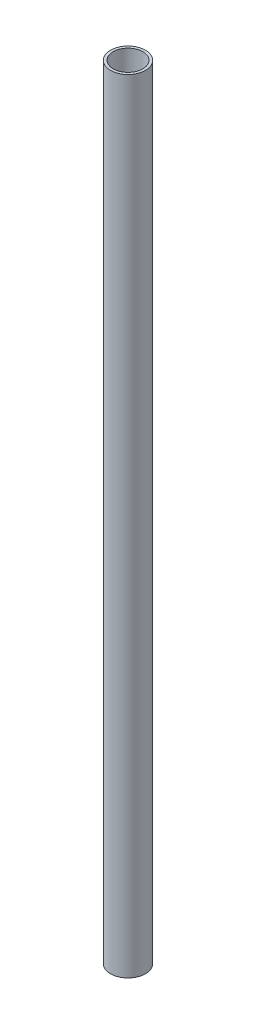
SolidWorks part; units mm, degrees
ref_plane "Front Plane" through (0, 0, 0) normal (0, 0, 1) x (1, 0, 0)
ref_plane "Top Plane" through (0, 0, 0) normal (0, 1, 0) x (1, 0, 0)
ref_plane "Right Plane" through (0, 0, 0) normal (1, 0, 0) x (0, 0, -1)
sketch "Sketch1" plane through (0, 0, 0) normal (0, 1, 0) x (1, 0, 0)
  circle A0 centre (0, 0) radius 3.35
  circle A1 centre (0, 0) radius 2.85
  dimension "D1" = 6.7
  dimension "D2" = 5.7
extrude "Boss-Extrude1" add sketch "Sketch1" along normal blind 150
